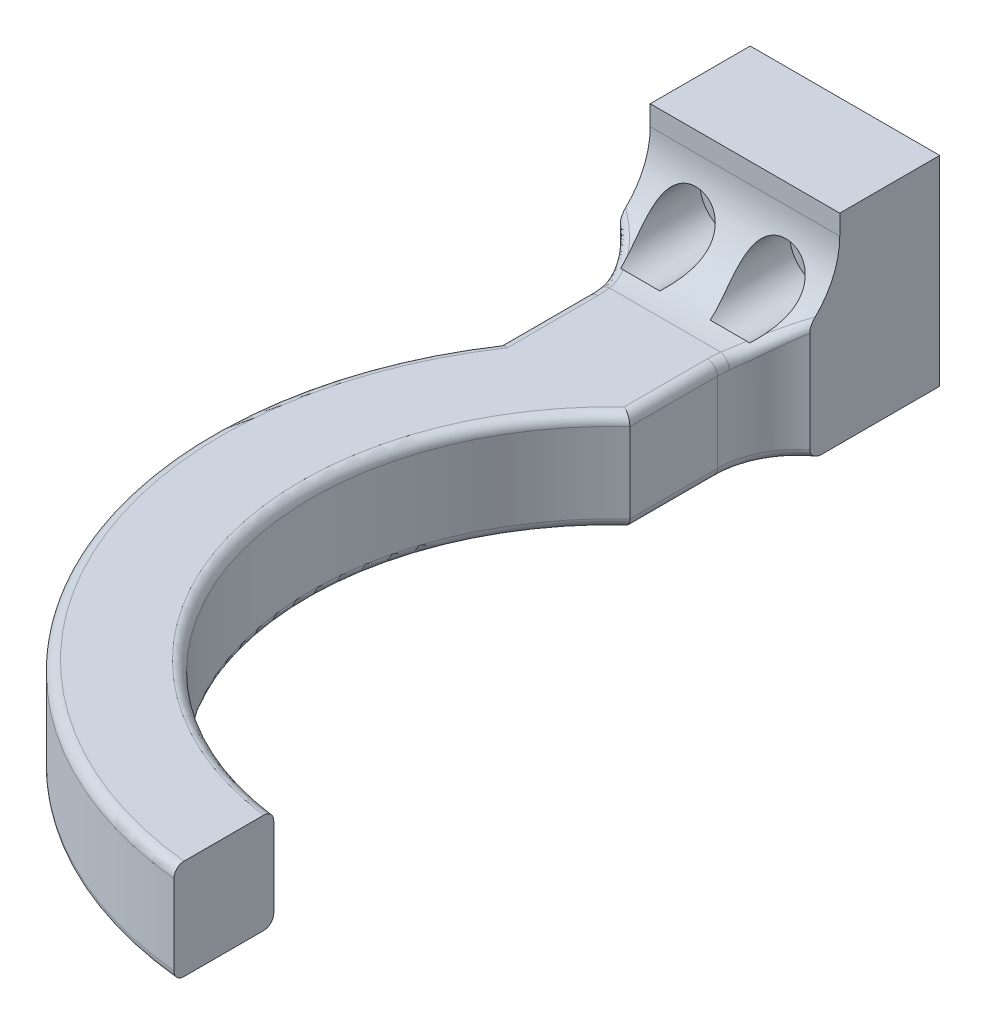
SolidWorks part; units mm, degrees
ref_plane "Front Plane" through (0, 0, 0) normal (0, 0, 1) x (1, 0, 0)
ref_plane "Top Plane" through (0, 0, 0) normal (0, 1, 0) x (1, 0, 0)
ref_plane "Right Plane" through (0, 0, 0) normal (1, 0, 0) x (0, 0, -1)
sketch "Sketch1" plane through (0, 0, 0) normal (0, 0, 1) x (1, 0, 0)
  line L0 (-15.1944, -0.9494) -> (3.7656, -0.9494)
  line L1 (-15.1944, 9.0506) -> (3.7656, 9.0506)
  line L2 (-15.1944, 9.0506) -> (-15.1944, -10.9494)
  line L3 (-15.1944, -10.9494) -> (3.7656, -10.9494)
  line L4 (3.7656, 9.0506) -> (3.7656, -10.9494)
  line L5 (-15.1944, -5.9494) -> (3.7656, -5.9494)
  dimension "D1" = 18.96
  dimension "D2" = 20
extrude "Boss-Extrude1" add sketch "Sketch1" against normal blind 10 contours L4 L1 L2 | L2 L5 L4 | L5 L2 L3 L4 region at (-5.7144, 4.0506, 0) region at (-5.7144, -3.4494, 0) region at (-5.7144, -8.4494, 0)
extrude "Boss-Extrude3" add sketch "Sketch1<4>" along normal blind 3 contours L2 L5 L4 L0 | L5 L2 L3 L4 region at (-5.7144, -3.4494, 0) region at (-5.7144, -8.4494, 0)
sketch "Sketch1<4>" plane through (0, 0, 0) normal (0, 0, 1) x (1, 0, 0) same geometry as "Sketch1"
ref_plane "Plane3" through (0, 0, 3) normal (0, 0, 1) x (1, 0, 0)
sketch "Sketch3" plane through (0, 0, 3) normal (0, 0, 1) x (1, 0, 0)
  line L0 (-15.1944, -0.9494) -> (3.7656, -0.9494)
  line L1 (3.7656, -0.9494) -> (3.7656, -10.9494)
  line L2 (3.7656, -10.9494) -> (-15.1944, -10.9494)
  line L3 (-15.1944, -10.9494) -> (-15.1944, -0.9494)
  line L4 (0.7656, -0.9494) -> (0.7656, -10.9494)
  line L5 (-12.1944, -0.9494) -> (-12.1944, -10.9494)
  dimension "D1" = 3
  dimension "D2" = 3
extrude "Boss-Extrude4" add sketch "Sketch3" along normal blind 15 contours L0 L5 L2 L4 region at (-5.7144, -5.9494, 3)
sketch "Sketch4" plane through (0, -0.9494, 0) normal (0, 1, 0) x (1, 0, 0)
  line L0 (0.7656, -18) -> (0.7656, -5.7152)
  line L1 (0.7656, -18) -> (0.7656, -3) construction
  line L4 (21.1092, -70.2343) -> (21.1092, -80.1555)
  arc A1 (0.7656, -18) -> (21.1092, -70.2343) centre (21.1092, -40.1555) ccw
  arc A2 (0.7656, -5.7152) -> (21.1092, -80.1555) centre (21.1092, -40.1555) ccw
extrude "Boss-Extrude5" add sketch "Sketch4" against normal blind 10
ref_plane "Plane4" through (21.1092, 0, 0) normal (1, 0, 0) x (0, 0, -1)
sketch "Sketch5" plane through (21.1092, 0, 0) normal (1, 0, 0) x (0, 0, -1)
  line L1 (-88.9708, 4.6934) -> (-65.8059, 4.6934)
  line L2 (-88.9708, 4.6934) -> (-88.9708, -18.3699)
  line L3 (-88.9708, -18.3699) -> (-65.8059, -18.3699)
  line L4 (-65.8059, 4.6934) -> (-65.8059, -18.3699)
extrude "Cut-Extrude1" cut sketch "Sketch5" against normal blind 4
fillet "Fillet1" radius 8 1 edges at (-5.7144, -0.9494, 0)
fillet "Fillet2" radius 8 2 edges at (-12.1944, -5.0719, 3) (0.7656, -5.0719, 3)
fillet "Fillet3" radius 1 14 edges at (1.5545, -10.9494, 5.7809) (-12.9833, -10.9494, 5.7809) (-13.5098, -0.3031, 4.85) (-12.2188, -0.9494, 8.6206) (1.5108, -0.6615, 5.8732) (0.79, -0.9494, 8.6206) (0.7656, -10.9494, 13.6225) (-7.584, -10.9494, 49.1795) (-15.0501, -10.9494, 57.2583) (-12.1944, -10.9494, 13.6225) (-12.1944, -0.9494, 13.6225) (-15.0501, -0.9494, 57.2583) (0.7656, -0.9494, 13.6225) (-7.584, -0.9494, 49.1795)
ref_plane "Plane5" through (0, 0, 0) normal (0, 0, 1) x (1, 0, 0)
sketch "Sketch6" plane through (0, 0, 0) normal (0, 0, 1) x (1, 0, 0)
  line L0 (3.7656, 1.5506) -> (-15.1944, 1.5506) construction
  line L1 (3.7656, 9.0506) -> (3.7656, -10.9494) construction
  line L2 (-15.1944, 9.0506) -> (-15.1944, -10.9494) construction
  line L3 (-15.1944, 9.0506) -> (3.7656, 9.0506) construction
  circle A0 centre (-10.2144, 1.5506) radius 1.5
  circle A1 centre (-10.2144, 1.5506) radius 3
  circle A2 centre (-1.2144, 1.5506) radius 1.5
  circle A3 centre (-1.2144, 1.5506) radius 3
  point P14 (0, 0)
  dimension "D2" = 9
  dimension "D1" = 7.5
  dimension "D3" = 4.98
extrude "Cut-Extrude5" cut sketch "Sketch6" against normal blind 17 and the other way blind 6 contours A0 | A2
extrude "Cut-Extrude7" cut sketch "Sketch6<6>" against normal blind 3 and the other way blind 6 contours A3 | A1
sketch "Sketch6<6>" plane through (0, 0, 0) normal (0, 0, 1) x (1, 0, 0) same geometry as "Sketch6"
